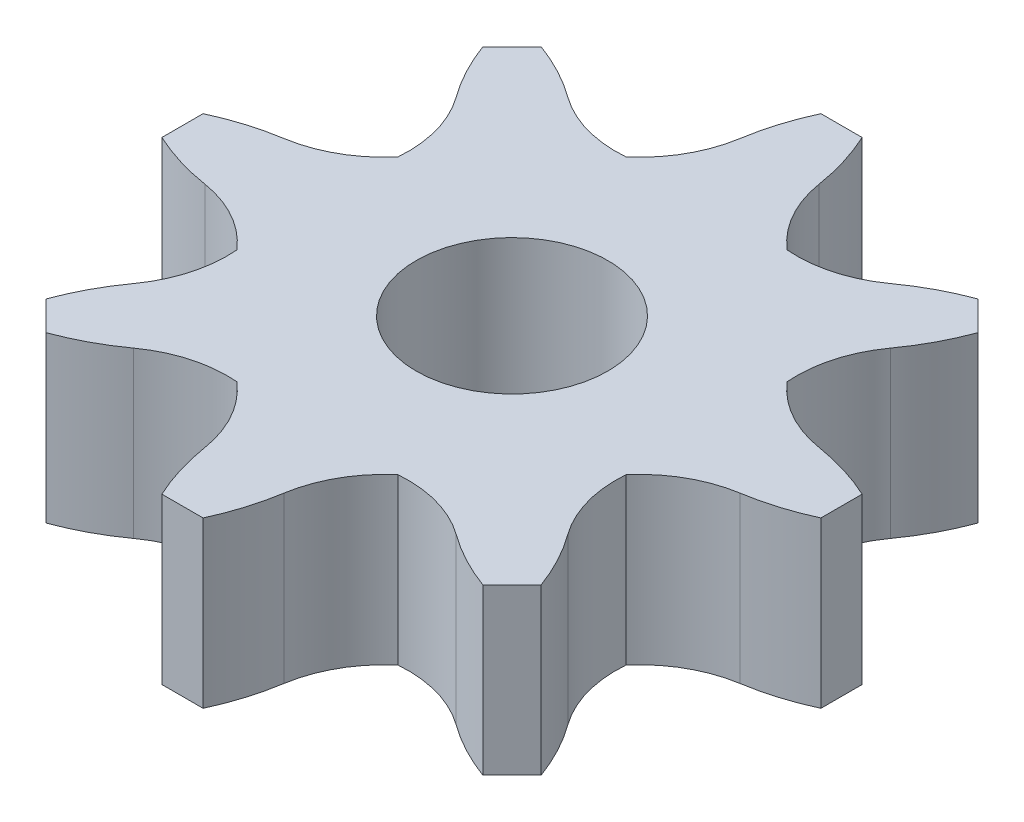
SolidWorks part; units mm, degrees
ref_plane "Front Plane" through (0, 0, 0) normal (0, 0, 1) x (1, 0, 0)
ref_plane "Top Plane" through (0, 0, 0) normal (0, 1, 0) x (1, 0, 0)
ref_plane "Right Plane" through (0, 0, 0) normal (1, 0, 0) x (0, 0, -1)
sketch "Sketch1" plane through (0, 0, 0) normal (0, 1, 0) x (1, 0, 0)
  line L2 (0.5, 7.9938) -> (-0.5, 7.9938)
  line L3 (-1, 4.9938) -> (1, 4.9938)
  line L4 (0, 7.9938) -> (0, 4.9938)
  line L6 (0, -2.325) -> (0, 2.325)
  line L7 (-0.8849, -2.15) -> (0.8849, -2.15)
  line L8 (0, 6.4938) -> (0.9583, 6.4938)
  line L9 (0, 6.4938) -> (-0.9583, 6.4938)
  line L10 (-2, 4.6838) -> (2, 4.6838)
  circle A0 centre (0, 0) radius 5.093
  arc A1 (-1, 4.9938) -> (-0.5, 7.9938) centre (4.6965, 5.5861) cw
  arc A2 (0.5, 7.9938) -> (1, 4.9938) centre (-4.6965, 5.5861) cw
  circle A3 centre (0, 0) radius 2.325
  arc A4 (-0.9583, 6.4938) -> (-2, 4.6838) centre (-3.8614, 6.9598) cw
  arc A5 (0.9583, 6.4938) -> (2, 4.6838) centre (3.8614, 6.9598) ccw
  dimension "D4" = 5.7272
  dimension "D5" = 10.1859
  dimension "D6" = 4.65
  dimension "D1" = 3
  dimension "D2" = 2
  dimension "D3" = 1
  dimension "D7" = 0.175
  dimension "D8" = 4
extrude "Boss-Extrude1" add sketch "Sketch1" along normal blind 4 contours A1 L2 A2 L3 | L10 A5 L8 L9 A4
sketch "Sketch4" plane through (0, 0, 0) normal (1, 0, 0) x (0, 0, -1)
  line L0 (0, 0) -> (0, 7.6311)
pattern_circular "CirPattern2" count 8 over 360 about axis through (0, 0, 0) along (0, 1, 0) of "Boss-Extrude1" reverse direction yes
extrude "Boss-Extrude3" add sketch "Sketch1<5>" along normal blind 4 contours L10 A0 A3 region at (4.1321, 0, -2.7286)
sketch "Sketch1<5>" plane through (0, 0, 0) normal (0, 1, 0) x (1, 0, 0) same geometry as "Sketch1"
equation "\"teeth\"= 8'num of teeth in gear"
equation "\"gearRadius\"= \"teeth\" * 4 / ( 2 * Pi )"
equation "\"D5@Sketch1\"=\"gearRadius\"*2"
equation "\"D1@CirPattern2\"=\"teeth\""
equation "\"thickness\"= 6"
equation "\"D1@Boss-Extrude1\"=\"thickness\""
equation "\"D1@Boss-Extrude3\"=\"thickness\""
